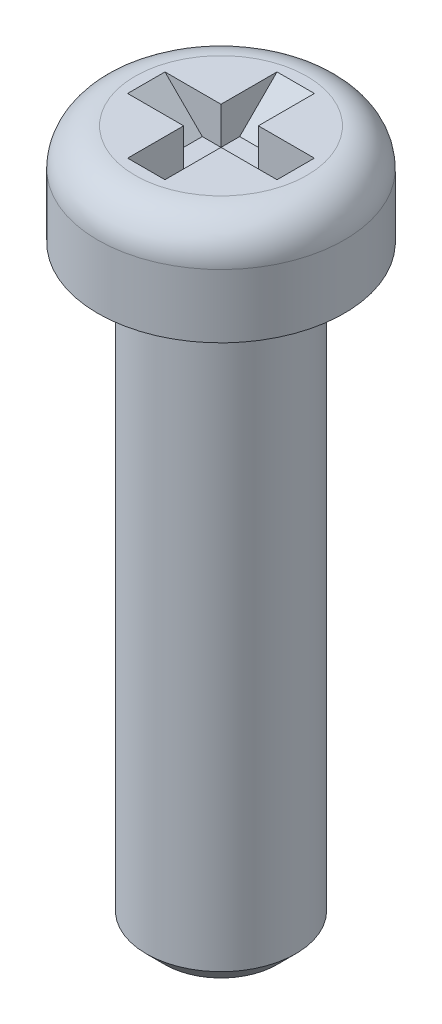
SolidWorks part; units mm, degrees
ref_plane "前视基准面" through (0, 0, 0) normal (0, 0, 1) x (1, 0, 0)
ref_plane "上视基准面" through (0, 0, 0) normal (0, 1, 0) x (1, 0, 0)
ref_plane "右视基准面" through (0, 0, 0) normal (1, 0, 0) x (0, 0, -1)
other "Configuration Table"
sketch "草图1" plane through (0, 0, 0) normal (0, 1, 0) x (1, 0, 0)
  circle A0 centre (0, 0) radius 2
  dimension "D1" = 4
extrude "凸台-拉伸1" add sketch "草图1" along normal blind 16
cosmetic thread "装饰螺纹线1" parameters "D2"=3
sketch "草图2" plane through (0, 16, 0) normal (0, 1, 0) x (1, 0, 0)
  circle A0 centre (0, 0) radius 3.3
  dimension "D1" = 6.6
extrude "凸台-拉伸2" add sketch "草图2" along normal blind 2.7
fillet "圆角1" radius 1 1 edges at (0, 18.7, 3.3)
chamfer "倒角1" distance 0.5 angle 45 1 edges at (0, 0, 2)
sketch "草图3" plane through (0, 18.7, 0) normal (0, 1, 0) x (1, 0, 0)
  line L0 (-2, 0) -> (2, 0)
  line L1 (0, 2) -> (0, -2)
  point P5 (0, 0)
  point P9 (0, 0)
  dimension "D1" = 4
  dimension "D2" = 4
extrude "切除-拉伸-薄壁1" cut sketch "草图3" against normal blind 1 thin thin type mid plane wall 1
chamfer "倒角2" distance 1 angle 45 4 edges at (0, 17.7, 2) (2, 17.7, 0) (0, 17.7, -2) (-2, 17.7, 0)
